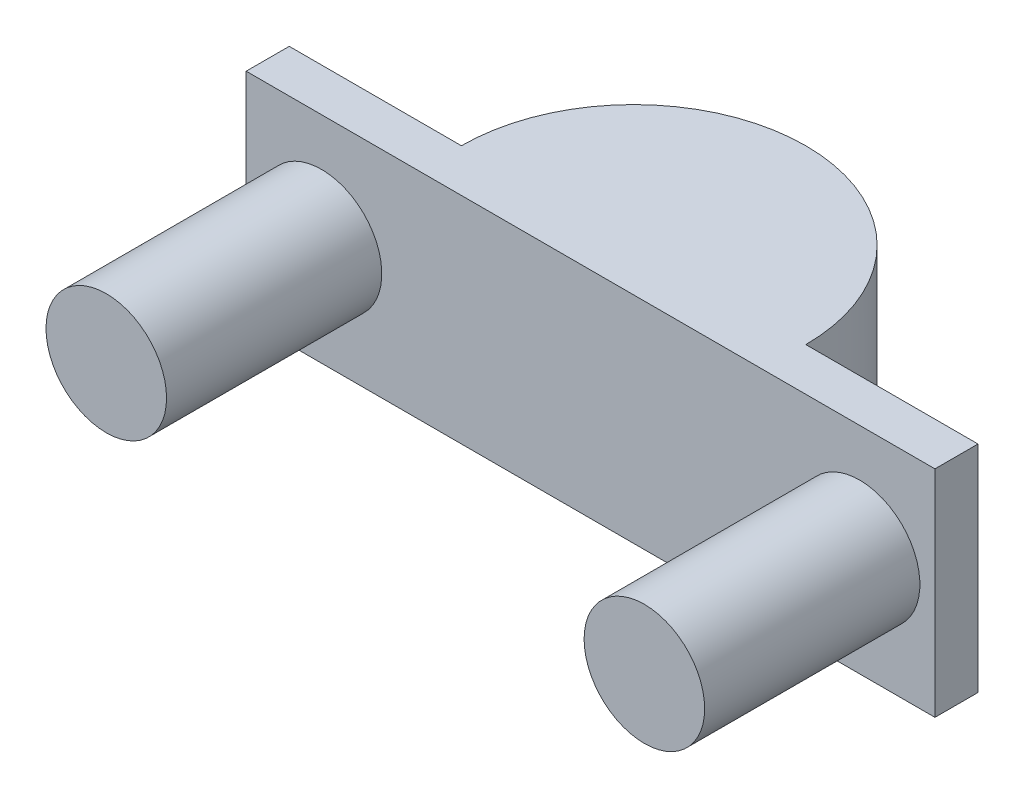
SolidWorks part; units mm, degrees
ref_plane "Front Plane" through (0, 0, 0) normal (0, 0, 1) x (1, 0, 0)
ref_plane "Top Plane" through (0, 0, 0) normal (0, 1, 0) x (1, 0, 0)
ref_plane "Right Plane" through (0, 0, 0) normal (1, 0, 0) x (0, 0, -1)
sketch "Sketch1" plane through (0, 0, 0) normal (0, 0, 1) x (1, 0, 0)
  line L1 (-16, -5) -> (16, -5)
  line L2 (-16, -5) -> (-16, 5)
  line L3 (-16, 5) -> (16, 5)
  line L4 (16, -5) -> (16, 5)
  line L5 (-16, -5) -> (16, 5) construction
  line L6 (-16, 5) -> (16, -5) construction
  point P0 (0, 0)
  dimension "D1" = 10
  dimension "D2" = 32
extrude "Boss-Extrude1" add sketch "Sketch1" along normal mid plane 2
sketch "Sketch2" plane through (0, 0, 1) normal (0, 0, 1) x (1, 0, 0)
  circle A0 centre (-12.5, 0) radius 2.8
  circle A1 centre (12.5, 0) radius 2.8
  point P4 (0, 0)
  point P6 (0, 0)
  point P7 (0, 0)
  dimension "D1" = 5.6
  dimension "D2" = 5.6
  dimension "D3" = 25
  dimension "D4" = 12.5
extrude "Boss-Extrude2" add sketch "Sketch2" along normal blind 10
sketch "Sketch3" plane through (0, 5, 0) normal (0, 1, 0) x (1, 0, 0)
  line L0 (16, 1) -> (-16, 1) construction
  line L1 (-8, 1) -> (8, 1)
  arc A0 (-8, 1) -> (8, 1) centre (0, 1) cw
  dimension "D3" = 8
  dimension "D1" = 8
  dimension "D2" = 8
extrude "Boss-Extrude3" add sketch "Sketch3" against normal up to surface (10 mm away) contours A0 L1 up to face at (0, -5, 0)
fillet "Fillet1" radius 4 1 edges at (0, -5, -9) second distance 7 first distance on face at (0, 0, -5)
